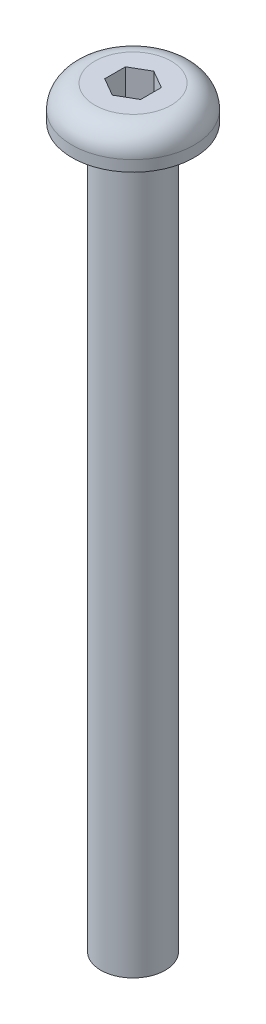
SolidWorks part; units mm, degrees
ref_plane "Front Plane" through (0, 0, 0) normal (0, 0, 1) x (1, 0, 0)
ref_plane "Top Plane" through (0, 0, 0) normal (0, 1, 0) x (1, 0, 0)
ref_plane "Right Plane" through (0, 0, 0) normal (1, 0, 0) x (0, 0, -1)
sketch "Sketch1" plane through (0, 0, 0) normal (0, 1, 0) x (1, 0, 0)
  circle A0 centre (0, 0) radius 1.4224
  dimension "D1" = 2.8448
extrude "Boss-Extrude1" add sketch "Sketch1" along normal blind 31.75
sketch "Sketch2" plane through (0, 31.75, 0) normal (0, 1, 0) x (1, 0, 0)
  circle A0 centre (0, 0) radius 2.7051
  dimension "D1" = 5.4102
extrude "Boss-Extrude2" add sketch "Sketch2" along normal blind 1.4986
fillet "Fillet1" radius 1.016 1 edges at (0, 33.2486, 2.7051)
sketch "Sketch3" plane through (0, 33.2486, 0) normal (0, 1, 0) x (1, 0, 0)
  line L1 (0, 0.9165) -> (-0.7937, 0.4583)
  line L2 (-0.7937, 0.4583) -> (-0.7937, -0.4583)
  line L3 (-0.7937, -0.4583) -> (0, -0.9165)
  line L4 (0, -0.9165) -> (0.7938, -0.4583)
  line L5 (0.7938, -0.4583) -> (0.7938, 0.4583)
  line L6 (0.7938, 0.4583) -> (0, 0.9165)
  circle A0 centre (0, 0) radius 0.7937 construction
  dimension "D1" = 1.5875
extrude "Cut-Extrude1" cut sketch "Sketch3" against normal blind 2.3813
